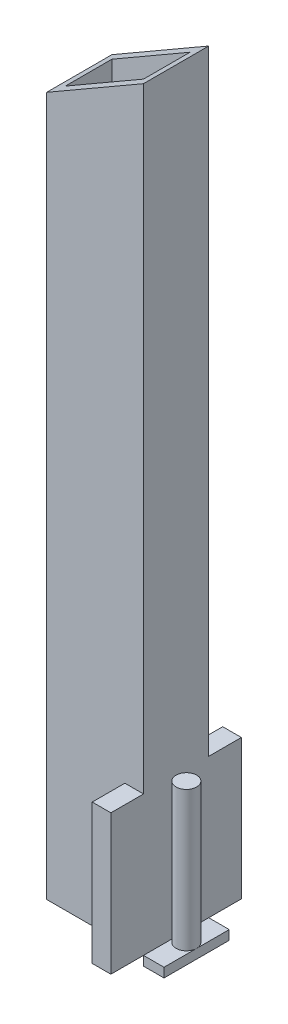
SolidWorks part; units mm, degrees
ref_plane "Front Plane" through (0, 0, 0) normal (0, 0, 1) x (1, 0, 0)
ref_plane "Top Plane" through (0, 0, 0) normal (0, 1, 0) x (1, 0, 0)
ref_plane "Right Plane" through (0, 0, 0) normal (1, 0, 0) x (0, 0, -1)
sketch "Sketch2" plane through (0, 0, 0) normal (0, 0, 1) x (1, 0, 0)
  line L0 (0, -32.5217) -> (0, 47.4783) construction
  line L1 (0, 0) -> (0, 75)
  line L2 (0, 75) -> (10.3923, 81)
  line L3 (0, 75) -> (16.7281, 75) construction
  line L4 (10.3923, 81) -> (10.3923, 0)
  line L5 (10.3923, 0) -> (0, 0)
  dimension "D1" = 75
  dimension "D2" = 12
  dimension "D3" = 30
extrude "Boss-Extrude1" add sketch "Sketch2" along normal mid plane 7
shell "Shell1" thickness 1 removed face at (5.1962, 0, 0) removed face at (5.1962, 78, 0)
sketch "Sketch3" plane through (0, 0, 0) normal (0, 1, 0) x (1, 0, 0)
  line L0 (10.3923, 3.5) -> (10.3923, -3.5) construction
  line L1 (0, 0) -> (10.3923, 0) construction
  line L2 (0, -3.5) -> (0, 3.5) construction
  line L3 (10.3923, -7) -> (10.3923, 7)
  line L4 (10.3923, 0) -> (11.4923, 0) construction
  line L5 (10.3923, 7) -> (8.3923, 7)
  line L6 (8.3923, 7) -> (8.3923, 3.5)
  line L7 (10.3923, 3.5) -> (0, 3.5) construction
  line L8 (8.3923, -3.5) -> (8.3923, -7)
  line L9 (10.3923, -3.5) -> (0, -3.5) construction
  line L10 (8.3923, -7) -> (10.3923, -7)
  line L11 (8.3923, 3.5) -> (10.3923, 3.5)
  line L12 (8.3923, -3.5) -> (10.3923, -3.5)
  line L13 (10.3923, 3.5) -> (12.5923, 3.5)
  line L14 (12.5923, 3.5) -> (12.5923, -3.5)
  line L15 (12.5923, -3.5) -> (10.3923, -3.5)
  circle A0 centre (11.4923, 0) radius 1.1
  point P11 (10.3923, 0)
  dimension "D3" = 1.1
  dimension "D1" = 7
  dimension "D2" = 1.1
  dimension "D4" = 2
  dimension "D5" = 2.2
extrude "Boss-Extrude2" add sketch "Sketch3" along normal blind 15 contours L6 L11 L3 L5 | L12 L8 L10 L3 | A0 region at (9.3923, 0, 5.25) region at (9.3923, 0, -5.25)
extrude "Boss-Extrude5" add sketch "Sketch3<6>" against normal blind 1 contours A0 L14 L13 L3 | A0 L3 L15 L14 | A0 region at (11.4923, 0, 2.1705) region at (11.4923, 0, -2.1705) region at (11.4923, 0, 0)
sketch "Sketch3<6>" plane through (0, 0, 0) normal (0, 1, 0) x (1, 0, 0) same geometry as "Sketch3"
